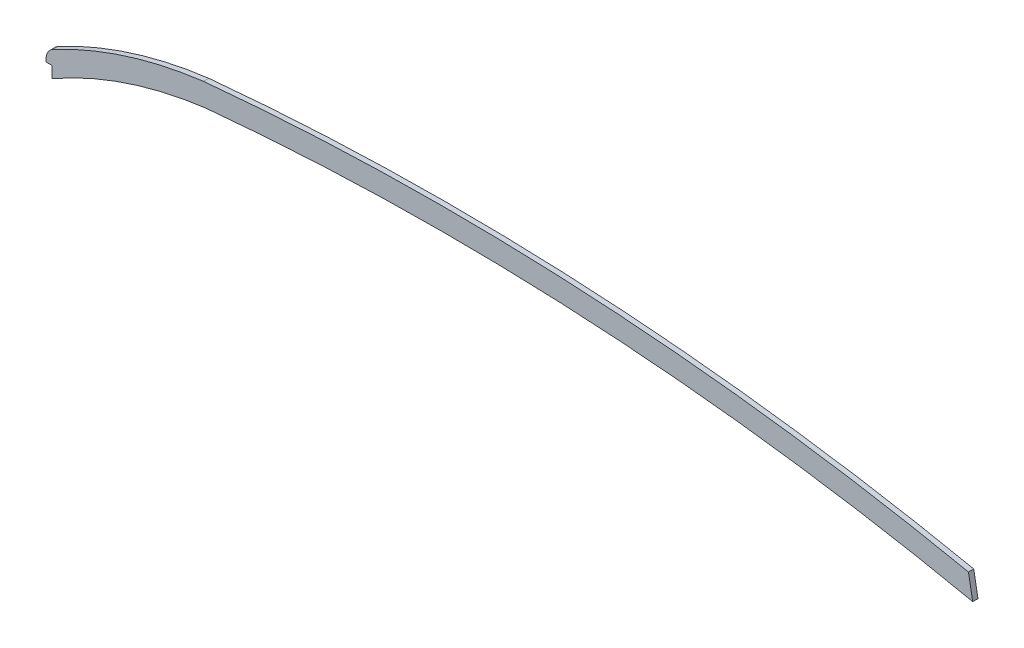
SolidWorks part; units mm, degrees
material "Balsa"
ref_plane "Front Plane" through (0, 0, 0) normal (0, 0, 1) x (1, 0, 0)
ref_plane "Top Plane" through (0, 0, 0) normal (0, 1, 0) x (1, 0, 0)
ref_plane "Right Plane" through (0, 0, 0) normal (1, 0, 0) x (0, 0, -1)
sketch "Sketch1" plane through (0, 0, 0) normal (0, 0, 1) x (1, 0, 0)
  line L0 (0, 101.6) -> (0, 100.0553)
  line L1 (0, -1.7463) -> (0, 1.7463) construction
  line L2 (0, 86.36) -> (8.1082, 86.36) construction
  line L3 (3.7499, 106.3536) -> (3.7499, -82.5359) construction
  line L4 (8.1082, 101.6) -> (0, 101.6) construction
  line L6 (3.7499, 93.1973) -> (0, 91.0322) construction
  line L7 (0, 99.5163) -> (0, 88.039) construction
  line L8 (558.2295, 97.6273) -> (555.6382, 111.8229)
  line L9 (0, 91.0322) -> (0, 86.36) construction
  line L10 (3.7499, 93.1973) -> (3.7499, 100.0553)
  line L11 (3.7499, 100.0553) -> (0, 97.8902) construction
  line L12 (0, 97.8902) -> (0, 91.0322) construction
  line L13 (3.7499, 100.0553) -> (0, 100.0553)
  line L14 (0, 100.0553) -> (0, 97.8902) construction
  line L26 (196.8609, -116.7457) -> (197.4984, -131.9724) construction
  line L28 (193.6887, -116.8786) -> (194.3262, -132.1052) construction
  line L32 (197.4984, -131.9724) -> (194.3262, -132.1052) construction
  line L41 (194.3262, -132.1052) -> (196.8609, -116.7457) construction
  line L42 (195.5936, -124.4255) -> (184.9758, 129.1656) construction
  line L70 (196.8609, -116.7457) -> (193.6887, -116.8786)
  line L72 (197.4984, -131.9724) -> (194.3262, -132.1052)
  line L74 (193.6887, -116.8786) -> (194.3262, -132.1052)
  line L78 (196.8609, -116.7457) -> (197.4984, -131.9724)
  line L79 (196.8609, -116.7457) -> (193.6887, -116.8786) construction
  arc A0 (4.3005, 108.7585) -> (94.8544, 137.376) centre (127, -121.92) cw
  arc A1 (4.3005, 108.7585) -> (0, 101.6) centre (8.1082, 101.6) ccw
  arc A2 (3.7499, 93.1973) -> (0, 86.36) centre (8.1082, 86.36) ccw construction
  arc A3 (94.8544, 137.376) -> (555.6382, 111.8229) centre (240.8652, -1397) cw
  arc A4 (3.7499, 93.1973) -> (96.3112, 124.0967) centre (127, -121.92) cw
  arc A5 (96.3112, 124.0967) -> (184.9758, 129.9274) centre (240.8652, -1397) cw
  arc A6 (10.5733, 96.9655) -> (96.3112, 124.0967) centre (127, -121.92) cw construction
  arc A7 (94.4927, 137.3434) -> (3.7499, 106.3536) centre (112.883, -64.8553) ccw construction
  arc A8 (96.3112, 124.0967) -> (552.9103, 98.7469) centre (240.8652, -1397) cw construction
  arc A9 (4.3005, 108.7585) -> (94.8544, 137.376) centre (127, -121.92) cw construction
  arc A11 (94.8544, 137.376) -> (555.6382, 111.8229) centre (240.8652, -1397) cw construction
  arc A13 (556.7512, 105.7321) -> (99.1899, 122.2822) centre (270.5046, -1474.7614) ccw construction
  arc A18 (184.9758, 129.9274) -> (275.6985, 130.5528) centre (240.8652, -1397) cw
  arc A21 (275.6985, 130.5528) -> (558.2295, 97.6273) centre (240.8652, -1397) cw
  spline S0 degree 3 poles (981.3177, 1818.2675) (1139.722, 204.4849) (873.2182, 1.0169) (565.628, -88.9106) (559.2919, -90.7077) (-121.8164, -278.7114) (-929.5333, 36.0269) (-1233.6865, -867.5095) knots -11.664502 -11.664502 -11.664502 -11.664502 0.25 0.25 0.5 0.5 27.071012 27.071012 27.071012 27.071012 only from (590.8643, -81.3536) to (514.7143, -102.4537) construction
  spline S1 degree 3 poles (1062.5522, -1662.3274) (1783.386, 752.2598) (1192.007, 51.9761) (480.6823, -110.4688) (472.1454, -112.3347) (455.0337, -115.879) (446.4591, -117.5582) (433.5613, -119.8984) (429.2558, -120.648) (422.7903, -121.7356) (420.6337, -122.0915) (417.3979, -122.6188) (416.3191, -122.7935) (329.7173, -136.7537) (244.3749, -151.8452) (-150.7518, 1789.6158) knots -20.37019 -20.37019 -20.37019 -20.37019 0.25 0.25 0.5 0.5 0.75 0.75 0.875 0.875 0.9375 0.9375 0.96875 0.96875 3.445896 3.445896 3.445896 3.445896 only from (514.7143, -102.4537) to (412.003, -123.4859) construction
  spline S2 degree 3 poles (-1526.2092, 975.8893) (-966.7298, 244.4948) (-373.5074, -121.9571) (226.7788, -133.168) (266.5142, -132.8729) (279.7628, -132.6016) (299.6408, -131.9345) (306.2677, -131.6688) (319.5231, -131.0505) (326.1536, -130.6977) (943.6584, -93.7895) (1501.3881, 309.0053) (2017.121, 1001.2295) knots -5.168103 -5.168103 -5.168103 -5.168103 0.25 0.5 0.5 0.625 0.625 0.6875 0.6875 0.75 0.75 6.511417 6.511417 6.511417 6.511417 only from (94.4926, -125.8525) to (412.003, -123.4859) construction
  spline S3 degree 3 poles (82.8406, 1879.826) (-241.5287, 509.6599) (-195.4311, -0.6421) (32.0968, -110.0953) (39.5136, -113.1375) (50.922, -117.0433) (54.7721, -118.2354) (60.6197, -119.8556) (62.5829, -120.3681) (66.5243, -121.3341) (68.5001, -121.787) (343.1899, -180.4478) (711.1357, 326.3263) (1193.75, 1513.3939) knots -7.368418 -7.368418 -7.368418 -7.368418 0.25 0.25 0.5 0.5 0.625 0.625 0.6875 0.6875 0.75 0.75 9.354609 9.354609 9.354609 9.354609 only from (3.7499, -94.8626) to (94.4926, -125.8525) construction
  spline S6 degree 3 poles (590.8643, -81.3536) (584.5771, -83.3154) (578.2709, -85.2143) (565.628, -88.9106) (559.2919, -90.7077) (540.2459, -95.9648) (527.5015, -99.2922) (514.7143, -102.4537) knots 0 0 0 0 0.25 0.25 0.5 0.5 1 1 1 1 construction
  spline S7 degree 3 poles (514.7143, -102.4537) (506.2284, -104.5517) (497.724, -106.577) (480.6823, -110.4688) (472.1454, -112.3347) (455.0337, -115.879) (446.4591, -117.5582) (433.5613, -119.8984) (429.2558, -120.648) (422.7903, -121.7356) (420.6337, -122.0915) (417.3979, -122.6188) (416.3191, -122.7935) (414.1613, -123.1413) (413.0825, -123.3155) (412.003, -123.4859) knots 0 0 0 0 0.25 0.25 0.5 0.5 0.75 0.75 0.875 0.875 0.9375 0.9375 0.96875 0.96875 1 1 1 1 construction
  spline S8 degree 3 poles (94.4926, -125.8525) (120.9278, -128.4258) (173.8258, -132.179) (226.7788, -133.168) (266.5142, -132.8729) (279.7628, -132.6016) (299.6408, -131.9345) (306.2677, -131.6688) (319.5231, -131.0505) (326.1536, -130.6977) (359.2877, -128.7173) (385.6949, -126.4433) (412.003, -123.4859) knots 0 0 0 0 0.25 0.5 0.5 0.625 0.625 0.6875 0.6875 0.75 0.75 1 1 1 1 construction
  spline S9 degree 3 poles (3.7499, -94.8626) (10.597, -99.2271) (17.6385, -103.1401) (32.0968, -110.0953) (39.5136, -113.1375) (50.922, -117.0433) (54.7721, -118.2354) (60.6197, -119.8556) (62.5829, -120.3681) (66.5243, -121.3341) (68.5001, -121.787) (78.4043, -123.9021) (86.408, -125.1172) (94.4926, -125.8525) knots 0 0 0 0 0.25 0.25 0.5 0.5 0.625 0.625 0.6875 0.6875 0.75 0.75 1 1 1 1 construction
  spline S15 degree 3 poles (587.4426, -62.5747) (587.1827, -61.1511) (586.6535, -58.2526) (585.7873, -53.5174) (584.8512, -48.394) (583.8406, -42.8532) (582.7565, -36.9006) (581.5991, -30.5376) (580.1295, -22.4773) (578.3524, -12.6853) (576.2505, -1.1976) (574.1192, 10.4518) (571.9272, 22.5233) (569.819, 34.0829) (567.7342, 45.5019) (565.8232, 55.9911) (564.3841, 63.8754) (563.4512, 68.9947) (562.9209, 71.9076) (562.4102, 74.7138) (561.9192, 77.4122) (561.4478, 80.0018) (560.9959, 82.4822) (560.5637, 84.8528) (560.1512, 87.1138) (559.7582, 89.2651) (559.385, 91.3073) (559.0312, 93.2414) (558.6975, 95.0661) (558.3822, 96.7905) (558.1867, 97.8615) (558.0896, 98.3936) knots 0 0 0 0 0.031687 0.064515 0.098497 0.133644 0.169967 0.207478 0.246191 0.30842 0.370332 0.432609 0.495165 0.563925 0.620591 0.686243 0.746551 0.766006 0.785258 0.804303 0.823142 0.841774 0.860197 0.878411 0.896416 0.91421 0.931793 0.949164 0.966322 0.983268 1 1 1 1 construction
  dimension "D4" = 8.1082
  dimension "D2" = 127
  dimension "D8" = 1397
  dimension "D9" = 30
  dimension "D1" = 15.24
  dimension "D3" = 8.1082
  dimension "D5" = 8.1082
  dimension "D6" = 101.6
  dimension "D7" = 121.92
  dimension "D10" = 6.858
  dimension "D11" = 3.7499
extrude "Boss-Extrude1" add sketch "Sketch1" against normal blind 3.175 contours A21 L8 A3 A0 A1 L0 L13 L10 A4 A5 A18 region at (5.963, 102.8887, 0)
equation "\"slotwidth\"=0.167708"
